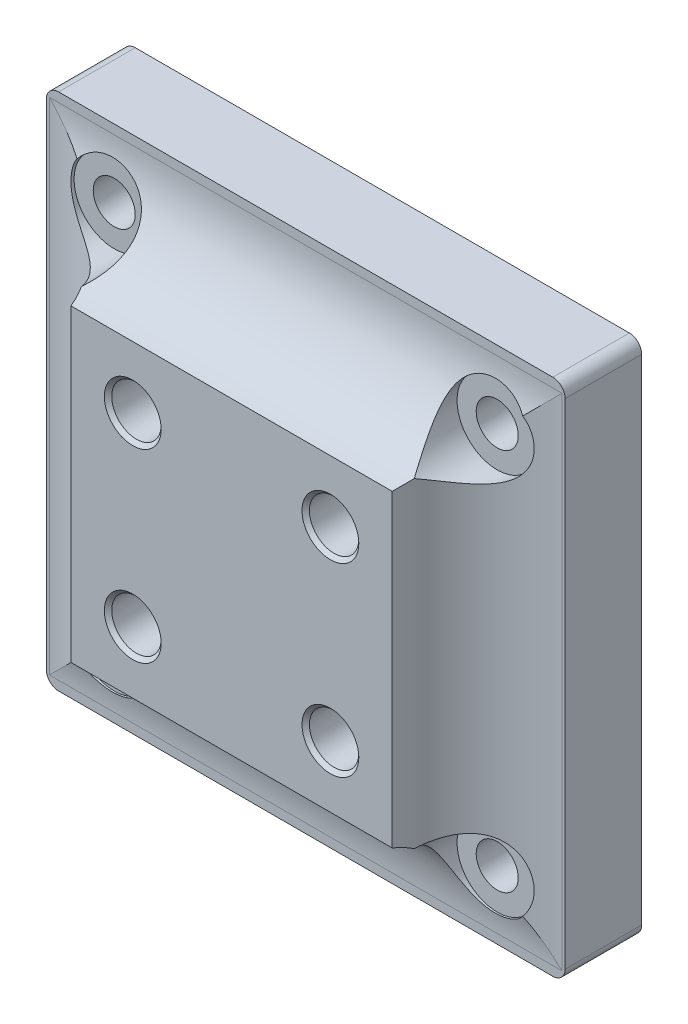
SolidWorks part; units mm, degrees
ref_plane "Front Plane" through (0, 0, 0) normal (0, 0, 1) x (1, 0, 0)
ref_plane "Top Plane" through (0, 0, 0) normal (0, 1, 0) x (1, 0, 0)
ref_plane "Right Plane" through (0, 0, 0) normal (1, 0, 0) x (0, 0, -1)
sketch "Sketch1" plane through (0, 0, 0) normal (0, 0, 1) x (1, 0, 0)
  line L0 (5.5, 5.5) -> (5.5, 36.5) construction
  line L1 (0, 0) -> (42, 0)
  line L2 (0, 0) -> (0, 42)
  line L3 (0, 42) -> (42, 42)
  line L4 (42, 0) -> (42, 42)
  line L5 (5.5, 36.5) -> (36.5, 36.5) construction
  line L6 (36.5, 5.5) -> (36.5, 36.5) construction
  line L7 (5.5, 5.5) -> (36.5, 5.5) construction
  line L8 (0, 21) -> (42, 21) construction
  line L9 (21, 42) -> (21, 0) construction
  line L11 (13, 13.5) -> (29, 13.5) construction
  line L12 (13, 13.5) -> (13, 28.5) construction
  line L13 (13, 28.5) -> (29, 28.5) construction
  line L14 (29, 13.5) -> (29, 28.5) construction
  line L15 (13, 13.5) -> (29, 28.5) construction
  line L16 (13, 28.5) -> (29, 13.5) construction
  circle A0 centre (5.5, 5.5) radius 1.7
  circle A1 centre (36.5, 5.5) radius 1.7
  circle A2 centre (36.5, 36.5) radius 1.7
  circle A3 centre (5.5, 36.5) radius 1.7
  circle A4 centre (13, 13.5) radius 3
  circle A5 centre (29, 13.5) radius 3
  circle A6 centre (29, 28.5) radius 3
  circle A7 centre (13, 28.5) radius 3
  point P20 (21, 21)
  dimension "D3" = 2
  dimension "D7" = 3.4
  dimension "D8" = 2
  dimension "D10" = 6
  dimension "D1" = 42
  dimension "D2" = 5.5
  dimension "D5" = 15
  dimension "D6" = 16
  dimension "D4" = 2
  dimension "D9" = 2
extrude "Boss-Extrude1" add sketch "Sketch1" along normal blind 6.2
sketch "Sketch2" plane through (0, 0, 6.2) normal (0, 0, 1) x (1, 0, 0)
  line L0 (13, 28.5) -> (29, 28.5) construction
  line L1 (29, 13.5) -> (29, 28.5) construction
  line L2 (13, 13.5) -> (29, 13.5) construction
  line L3 (13, 13.5) -> (13, 28.5) construction
  line L4 (13, 28.5) -> (29, 28.5) construction
  line L5 (29, 13.5) -> (29, 28.5) construction
  line L6 (13, 13.5) -> (29, 13.5) construction
  line L7 (13, 13.5) -> (13, 28.5) construction
  line L8 (8, 8.5) -> (8, 33.5)
  line L9 (8, 33.5) -> (34, 33.5)
  line L10 (34, 8.5) -> (34, 33.5)
  line L11 (8, 8.5) -> (34, 8.5)
  circle A9 centre (13, 13.5) radius 2
  circle A10 centre (29, 13.5) radius 2
  circle A11 centre (29, 28.5) radius 2
  circle A12 centre (13, 28.5) radius 2
  dimension "D2" = 2
  dimension "D4" = 4
  dimension "D1" = 5
  dimension "D3" = 2
extrude "Boss-Extrude2" add sketch "Sketch2" along normal blind 6
fillet "Fillet2" radius 8 4 edges at (21, 33.5, 6.2) (8, 21, 6.2) (21, 8.5, 6.2) (34, 21, 6.2)
sketch "Sketch3" plane through (0, 0, 12.2) normal (0, 0, 1) x (1, 0, 0)
  circle A0 centre (36.5, 36.5) radius 1.7 construction
  circle A1 centre (5.5, 36.5) radius 1.7 construction
  circle A2 centre (36.5, 5.5) radius 1.7 construction
  circle A3 centre (5.5, 5.5) radius 1.7 construction
  circle A4 centre (36.5, 36.5) radius 1.7 construction
  circle A5 centre (5.5, 36.5) radius 1.7 construction
  circle A6 centre (36.5, 5.5) radius 1.7 construction
  circle A7 centre (5.5, 5.5) radius 1.7 construction
  circle A8 centre (5.5, 36.5) radius 3.25
  circle A9 centre (36.5, 36.5) radius 3.25
  circle A10 centre (36.5, 5.5) radius 3.25
  circle A11 centre (5.5, 5.5) radius 3.25
  dimension "D1" = 6.5
  dimension "D2" = 2
  dimension "D3" = 2
extrude "Cut-Extrude1" cut sketch "Sketch3" against normal up to surface (6 mm away) up to face at (21, 21, 6.2)
chamfer "Chamfer1" distance 0.3 angle 45 4 edges at (31, 13.5, 12.2) (31, 28.5, 12.2) (15, 28.5, 12.2) (15, 13.5, 12.2)
fillet "Fillet3" radius 1 4 edges at (42, 42, 3.1) (0, 42, 3.1) (0, 0, 3.1) (42, 0, 3.1)
